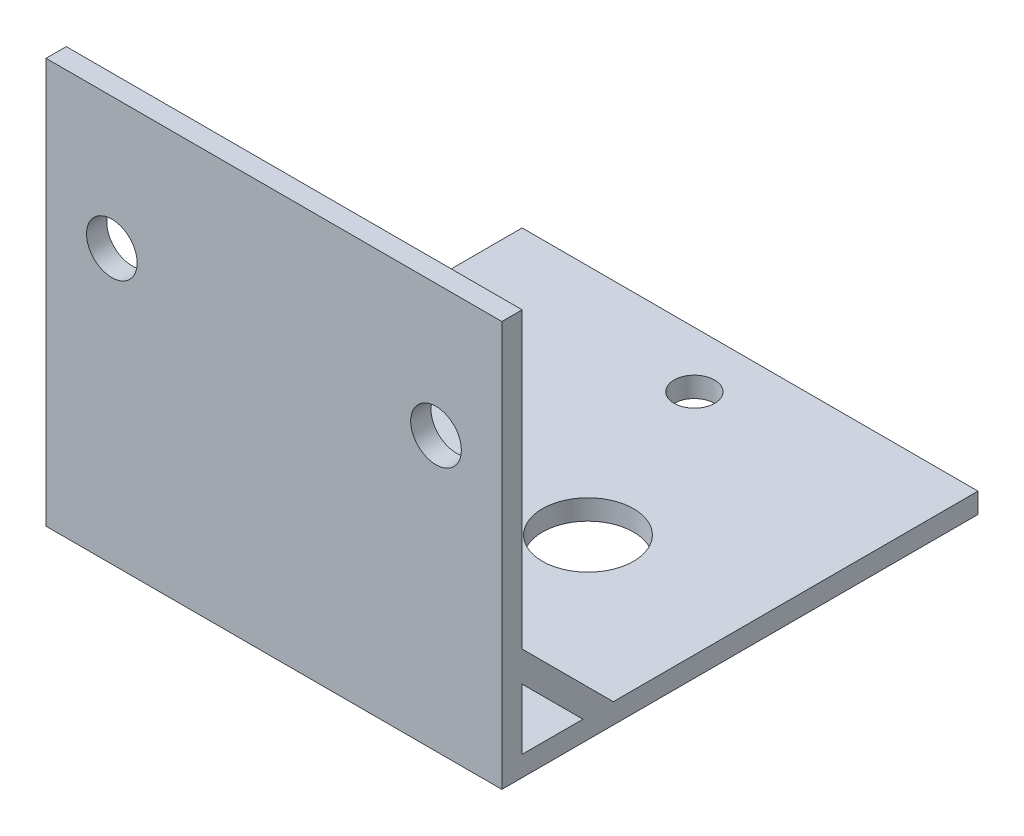
SolidWorks part; units mm, degrees
ref_plane "Front Plane" through (0, 0, 0) normal (0, 0, 1) x (1, 0, 0)
ref_plane "Top Plane" through (0, 0, 0) normal (0, 1, 0) x (1, 0, 0)
ref_plane "Right Plane" through (0, 0, 0) normal (1, 0, 0) x (0, 0, -1)
sketch "Sketch7" plane through (0, 0, 0) normal (0, 1, 0) x (1, 0, 0)
  line L0 (28.2563, -140.551) -> (-16.7437, -140.551)
  line L1 (28.2563, -95.551) -> (-16.7437, -95.551)
  line L2 (28.2563, -95.551) -> (28.2563, -142.551)
  line L3 (28.2563, -142.551) -> (-16.7437, -142.551)
  line L4 (-16.7437, -95.551) -> (-16.7437, -142.551)
  line L5 (28.2563, -95.551) -> (-16.7437, -142.551) construction
  line L6 (28.2563, -142.551) -> (-16.7437, -95.551) construction
  circle A0 centre (12.7563, -118.551) radius 4.5
  circle A1 centre (5.362, -118.9853) radius 14
  circle A2 centre (5.7563, -101.051) radius 2
  circle A3 centre (5.7563, -136.051) radius 2
  circle A4 centre (12.7563, -118.551) radius 3
  point P0 (5.7563, -119.051)
  dimension "D1" = 47
  dimension "D2" = 45
  dimension "D3" = 2
  dimension "D4" = 7
  dimension "D5" = 7
  dimension "D6" = 17.5
  dimension "D7" = 17.5
  dimension "D8" = 24
extrude "Boss-Extrude5" add sketch "Sketch7" along normal blind 2 separate body contours L1 L4 L0 L2 A3 A2 A1 | A1 A0 region at (5.7563, 0, 139.9146) region at (4.5101, 0, 119.0354)
extrude "Boss-Extrude6" add sketch "Sketch7<3>" along normal blind 40 contours L0 L4 L3 L2 region at (5.7563, 0, 141.551)
sketch "Sketch7<3>" plane through (0, 0, 0) normal (0, 1, 0) x (1, 0, 0) same geometry as "Sketch7"
sketch "Sketch8" plane through (-16.7437, 0, 0) normal (-1, 0, 0) x (0, 0, 1)
  line L0 (140.551, 8) -> (134.551, 2)
  line L1 (140.551, 40) -> (140.551, 2) construction
  line L2 (95.551, 2) -> (140.551, 2) construction
  line L3 (131.551, 2) -> (140.551, 11)
  line L4 (140.551, 11) -> (140.551, 8)
  line L5 (134.551, 2) -> (131.551, 2)
  dimension "D1" = 6
  dimension "D2" = 6
  dimension "D3" = 9
  dimension "D4" = 9
extrude "Boss-Extrude7" add sketch "Sketch8" against normal blind 2
ref_plane "Plane2" through (5.7563, 0, 0) normal (-1, 0, 0) x (0, 0, 1)
mirror "Mirror2" about plane through (5.7563, 0, 0) normal (-1, 0, 0) of "Boss-Extrude7"
sketch "Sketch9" plane through (0, 0, 142.551) normal (0, 0, 1) x (1, 0, 0)
  line L0 (5.7563, 22) -> (5.7563, -22) construction
  line L1 (-15.2437, 34) -> (26.7563, 34)
  line L2 (-15.2437, 34) -> (-15.2437, 20)
  line L3 (-15.2437, 20) -> (26.7563, 20)
  line L4 (26.7563, 34) -> (26.7563, 20)
  line L5 (-15.2437, 34) -> (26.7563, 20) construction
  line L6 (-15.2437, 20) -> (26.7563, 34) construction
  line L7 (28.2563, 0) -> (-16.7437, 0) construction
  point P0 (5.7563, 27)
  dimension "D1" = 20
  dimension "D2" = 14
  dimension "D3" = 42
sketch "Sketch10" plane through (0, 0, 142.551) normal (0, 0, 1) x (1, 0, 0)
  line L0 (26.7563, 34) -> (26.7563, 20) construction
  line L1 (-15.2437, 34) -> (26.7563, 34) construction
  line L2 (-15.2437, 34) -> (-15.2437, 20) construction
  circle A0 centre (21.7563, 27) radius 2.5
  circle A1 centre (-10.2437, 27) radius 2.5
  dimension "D1" = 5
  dimension "D2" = 5
  dimension "D4" = 5
  dimension "D3" = 7
  dimension "D5" = 7
  dimension "D6" = 5
extrude "Cut-Extrude2" cut sketch "Sketch10" against normal blind 2
